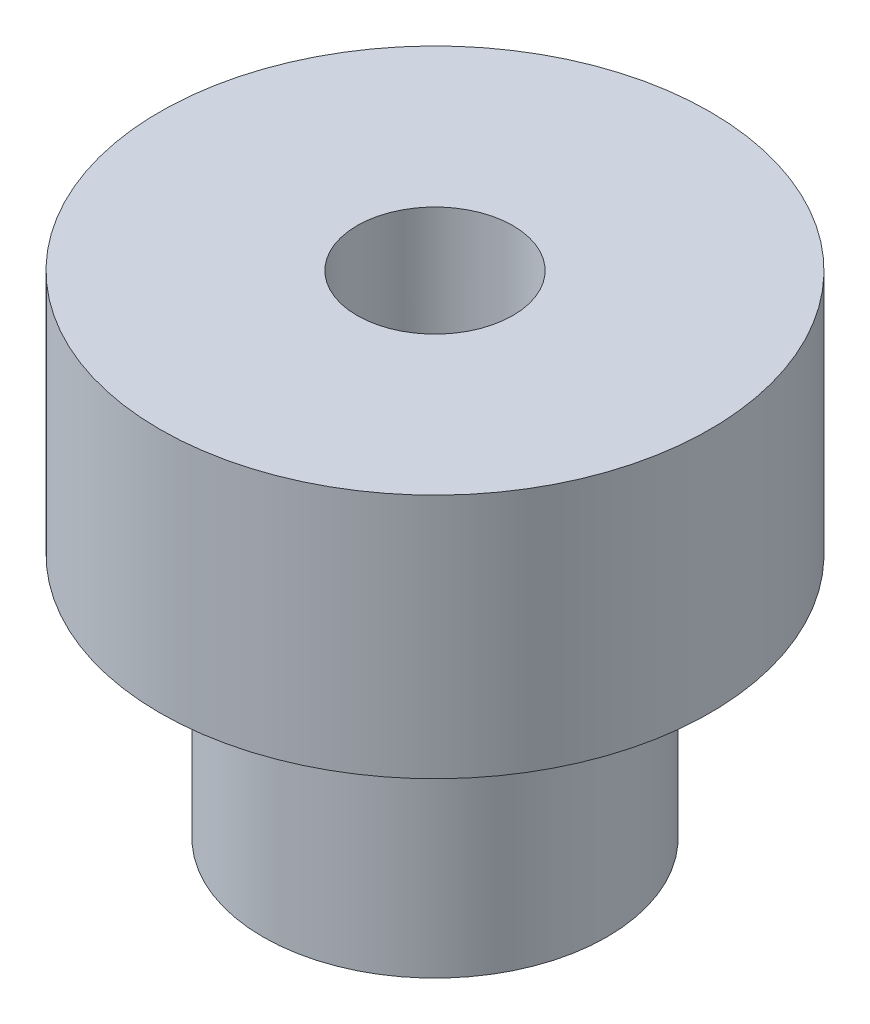
SolidWorks part; units mm, degrees
ref_plane "Front Plane" through (0, 0, 0) normal (0, 0, 1) x (1, 0, 0)
ref_plane "Top Plane" through (0, 0, 0) normal (0, 1, 0) x (1, 0, 0)
ref_plane "Right Plane" through (0, 0, 0) normal (1, 0, 0) x (0, 0, -1)
sketch "Sketch1" plane through (0, 0, 0) normal (0, 1, 0) x (1, 0, 0)
  circle A0 centre (0, 0) radius 5.6
  circle A1 centre (0, 0) radius 1.586
  dimension "D1" = 11.2
  dimension "D2" = 3.172
extrude "Boss-Extrude1" add sketch "Sketch1" along normal blind 5
sketch "Sketch2" plane through (0, 0, 0) normal (0, -1, 0) x (1, 0, 0)
  circle A0 centre (0, 0) radius 3.5
  circle A1 centre (0, 0) radius 1.586
  circle A2 centre (0, 0) radius 1.586 construction
  dimension "D1" = 7
extrude "Boss-Extrude2" add sketch "Sketch2" along normal blind 5
sketch "Sketch3" plane through (0, 0, 0) normal (1, 0, 0) x (0, 0, -1)
  line L0 (0, 0) -> (0, -5) construction
  line L1 (-3.5, -5) -> (3.5, -5) construction
  line L2 (-3.5, -2.5) -> (3.5, -2.5) construction
  line L3 (3.5, -5) -> (3.5, 0) construction
  circle A0 centre (0, -2.5) radius 1.25
  point P10 (0, -2.5)
  dimension "D1" = 2.5
extrude "Cut-Extrude1" cut sketch "Sketch3" against normal blind 10
